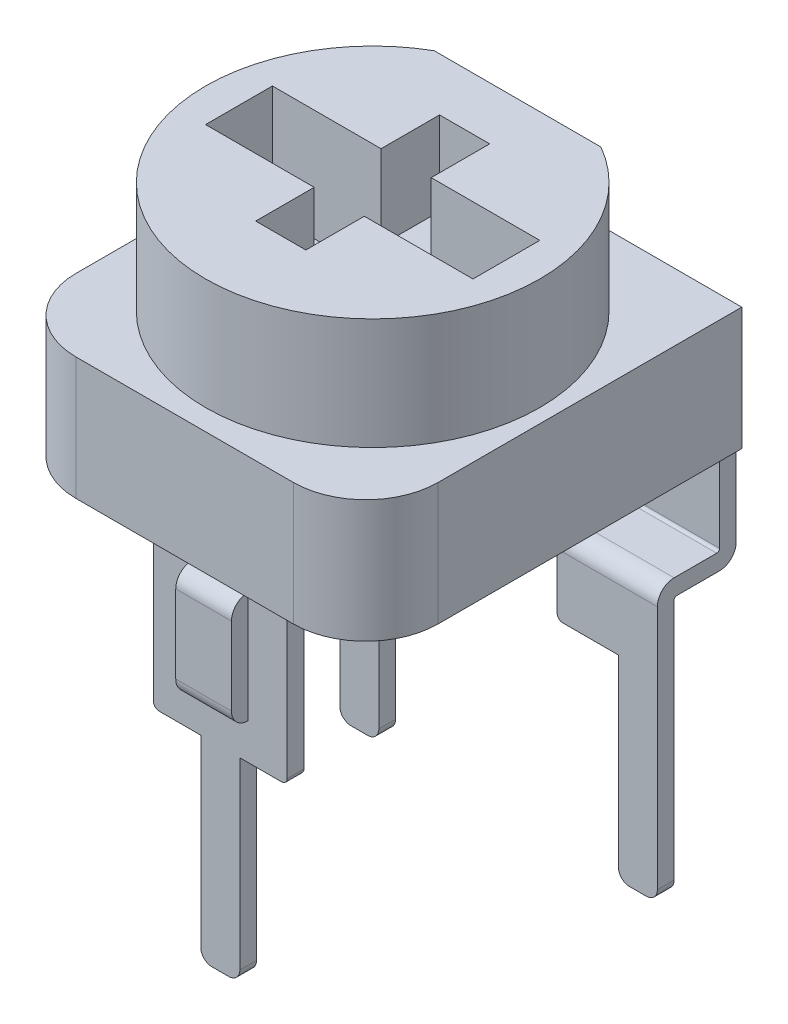
SolidWorks part; units mm, degrees
material "PVC Rigid"
ref_plane "Front Plane" through (0, 0, 0) normal (0, 0, 1) x (1, 0, 0)
ref_plane "Top Plane" through (0, 0, 0) normal (0, 1, 0) x (1, 0, 0)
ref_plane "Right Plane" through (0, 0, 0) normal (1, 0, 0) x (0, 0, -1)
sketch "Sketch1" plane through (0, 0, 0) normal (0, 1, 0) x (1, 0, 0)
  line L0 (-1.4967, 2.6) -> (1.4967, 2.6)
  arc A0 (-1.4967, 2.6) -> (1.4967, 2.6) centre (0, 0) ccw
  dimension "D1" = 6
  dimension "D2" = 2.6
extrude "Boss-Extrude1" add sketch "Sketch1" along normal blind 2
sketch "Sketch2" plane through (0, 2, 0) normal (0, 1, 0) x (1, 0, 0)
  line L1 (-2.4, -0.6) -> (2.4, -0.6)
  line L2 (-2.4, -0.6) -> (-2.4, 0.6)
  line L3 (-2.4, 0.6) -> (2.4, 0.6)
  line L4 (2.4, -0.6) -> (2.4, 0.6)
  line L5 (-2.4, -0.6) -> (2.4, 0.6) construction
  line L6 (-2.4, 0.6) -> (2.4, -0.6) construction
  point P0 (0, 0)
  point P6 (0, 0)
  dimension "D1" = 1.2
  dimension "D2" = 4.8
extrude "Cut-Extrude1" cut sketch "Sketch2" against normal through all
sketch "Sketch3" plane through (0, 2, 0) normal (0, 1, 0) x (1, 0, 0)
  line L1 (-0.45, -1.65) -> (0.45, -1.65)
  line L2 (-0.45, -1.65) -> (-0.45, 1.65)
  line L3 (-0.45, 1.65) -> (0.45, 1.65)
  line L4 (0.45, -1.65) -> (0.45, 1.65)
  line L5 (-0.45, -1.65) -> (0.45, 1.65) construction
  line L6 (-0.45, 1.65) -> (0.45, -1.65) construction
  point P0 (0, 0)
  dimension "D1" = 0.9
  dimension "D2" = 3.3
extrude "Cut-Extrude2" cut sketch "Sketch3" against normal blind 1.5
sketch "Sketch4" plane through (0, 0, 0) normal (0, -1, 0) x (1, 0, 0)
  line L1 (-3.25, -3.375) -> (3.25, -3.375)
  line L2 (-3.25, -3.375) -> (-3.25, 2.075)
  line L3 (-1.95, 3.375) -> (1.95, 3.375)
  line L4 (3.25, -3.375) -> (3.25, 2.075)
  line L5 (-3.25, -3.375) -> (2.8764, 2.987) construction
  line L6 (-2.8764, 2.987) -> (3.25, -3.375) construction
  arc A0 (-1.95, 3.375) -> (-3.25, 2.075) centre (-1.95, 2.075) ccw
  arc A1 (3.25, 2.075) -> (1.95, 3.375) centre (1.95, 2.075) ccw
  point P0 (0, 0)
  dimension "D3" = 1.95
  dimension "D4" = 6.5
  dimension "D1" = 2.6
  dimension "D2" = 2.075
  dimension "D5" = 3.375
extrude "Boss-Extrude2" add sketch "Sketch4" along normal blind 2.2 separate body
sketch "Sketch5" plane through (0, -2.2, 0) normal (0, -1, 0) x (1, 0, 0)
  line L1 (-1.2, 2.735) -> (1.2, 2.735)
  line L2 (-1.2, 2.735) -> (-1.2, 2.435)
  line L3 (-1.2, 2.435) -> (1.2, 2.435)
  line L4 (1.2, 2.735) -> (1.2, 2.435)
  line L5 (-1.2, 2.735) -> (1.2, 2.435) construction
  line L6 (-1.2, 2.435) -> (1.2, 2.735) construction
  point P0 (0, 2.585)
  dimension "D1" = 0.3
  dimension "D2" = 2.4
  dimension "D3" = 2.585
  dimension "D4" = 1.2
extrude "Boss-Extrude3" add sketch "Sketch5" along normal blind 3.2 separate body
sketch "Sketch6" plane through (0, -5.4, 0) normal (0, -1, 0) x (1, 0, 0)
  line L1 (-0.35, 2.435) -> (0.35, 2.435)
  line L2 (-0.35, 2.435) -> (-0.35, 2.735)
  line L3 (-0.35, 2.735) -> (0.35, 2.735)
  line L4 (0.35, 2.435) -> (0.35, 2.735)
  line L5 (-0.35, 2.435) -> (0.35, 2.735) construction
  line L6 (-0.35, 2.735) -> (0.35, 2.435) construction
  line L7 (1.2, 2.435) -> (1.2, 2.735) construction
  line L8 (1.2, 2.735) -> (-1.2, 2.735) construction
  point P0 (0, 2.585)
  dimension "D1" = 0.3
  dimension "D2" = 0.7
  dimension "D3" = 1.2
  dimension "D4" = 0.15
extrude "Boss-Extrude4" add sketch "Sketch6" along normal blind 3.5
fillet "Fillet1" radius 0.1 2 edges at (-1.2, -5.4, 2.585) (1.2, -5.4, 2.585)
fillet "Fillet2" radius 0.2 2 edges at (0.35, -8.9, 2.585) (-0.35, -8.9, 2.585)
sketch "Sketch8" plane through (0, 0, 2.735) normal (0, 0, 1) x (1, 0, 0)
  line L2 (-0.5, -2.75) -> (0.5, -2.75)
  line L3 (-0.5, -2.75) -> (-0.5, -4.75)
  line L4 (-0.5, -4.75) -> (0.5, -4.75)
  line L5 (0.5, -2.75) -> (0.5, -4.75)
  line L6 (-0.5, -2.75) -> (0.5, -4.75) construction
  line L8 (0, -2.2) -> (0, -8.9171) construction
  line L9 (-1.2, -3.75) -> (1.2, -3.75) construction
  line L10 (-1.2, -5.3) -> (-1.2, -2.2) construction
  line L11 (1.2, -5.3) -> (1.2, -2.2) construction
  line L12 (-0.5, -4.75) -> (0.5, -2.75) construction
  point P0 (0, -3.75)
  dimension "D1" = 1
  dimension "D2" = 2
extrude "Boss-Extrude5" add sketch "Sketch8" along normal blind 0.3
fillet "Fillet3" radius 0.3 2 edges at (0, -4.75, 3.035) (0, -2.75, 3.035)
sketch "Sketch16" plane through (0, 0, 2.435) normal (0, 0, -1) x (-1, 0, 0)
  line L0 (-0.4, -3.05) -> (0.4, -3.05)
  line L1 (-0.4, -3.05) -> (-0.4, -4.45)
  line L2 (-0.4, -4.45) -> (0.4, -4.45)
  line L3 (0.4, -3.05) -> (0.4, -4.45)
  line L4 (-0.4, -3.05) -> (0.4, -4.45) construction
  line L5 (0, -2.2) -> (0, -5.026) construction
  line L6 (1.2, -2.2) -> (-1.2, -2.2) construction
  line L7 (-0.4, -4.45) -> (0.4, -3.05) construction
  line L8 (-1.2, -3.75) -> (1.2, -3.75) construction
  line L9 (-1.2, -5.3) -> (-1.2, -2.2) construction
  line L10 (1.2, -5.3) -> (1.2, -2.2) construction
  point P0 (0, -3.75)
  dimension "D1" = 0.8
  dimension "D2" = 1.4
extrude "Cut-Extrude5" cut sketch "Sketch16" against normal blind 0.3
fillet "Fillet18" radius 0.3 2 edges at (0, -3.05, 2.735) (0, -4.45, 2.735)
sketch "Sketch9" plane through (0, 0, -3.375) normal (0, 0, -1) x (-1, 0, 0)
  line L1 (-2.85, -1) -> (-1.05, -1)
  line L2 (-2.85, -1) -> (-2.85, -4)
  line L3 (-2.85, -4) -> (-1.05, -4)
  line L4 (-1.05, -1) -> (-1.05, -4)
  line L5 (-2.85, -1) -> (-1.05, -4) construction
  line L6 (-2.85, -4) -> (-1.05, -1) construction
  line L9 (3.25, 0) -> (-3.25, 0) construction
  line L10 (0, 0) -> (0, -9.3004) construction
  line L11 (2.85, -1) -> (1.05, -4) construction
  line L12 (2.85, -4) -> (1.05, -1) construction
  line L13 (2.85, -4) -> (1.05, -4)
  line L14 (1.05, -1) -> (1.05, -4)
  line L15 (2.85, -1) -> (1.05, -1)
  line L16 (2.85, -1) -> (2.85, -4)
  point P0 (-1.95, -2.5)
  dimension "D1" = 1.8
  dimension "D2" = 3
  dimension "D3" = 1
  dimension "D4" = 2.1
extrude "Boss-Extrude6" add sketch "Sketch9" along normal blind 0.3 separate body
fillet "Fillet4" radius 0.3 1 edges at (1.95, -1, -3.675)
fillet "Fillet5" radius 0.3 1 edges at (-1.95, -1, -3.675)
sketch "Sketch10" plane through (0, -4, 0) normal (0, -1, 0) x (1, 0, 0)
  line L1 (-2.85, -3.675) -> (-1.05, -3.675)
  line L2 (-2.85, -3.675) -> (-2.85, -2.26)
  line L3 (-2.85, -2.26) -> (-1.05, -2.26)
  line L4 (-1.05, -3.675) -> (-1.05, -2.26)
  line L5 (1.05, -3.675) -> (2.85, -3.675)
  line L6 (1.05, -3.675) -> (1.05, -2.26)
  line L7 (1.05, -2.26) -> (2.85, -2.26)
  line L8 (2.85, -3.675) -> (2.85, -2.26)
  dimension "D1" = 1.415
  dimension "D2" = 1.8
  dimension "D3" = 1.415
  dimension "D4" = 1.8
extrude "Boss-Extrude7" add sketch "Sketch10" along normal blind 0.3
fillet "Fillet6" radius 0.3 1 edges at (-1.95, -4.3, -3.675)
fillet "Fillet7" radius 0.3 1 edges at (1.95, -4.3, -3.675)
fillet "Fillet8" radius 0.05 1 edges
fillet "Fillet9" radius 0.05 1 edges
sketch "Sketch11" plane through (0, -4.3, 0) normal (0, -1, 0) x (1, 0, 0)
  line L0 (-1.05, -3.375) -> (-1.05, -2.26) construction
  line L1 (-2.85, -2.26) -> (-1.05, -2.26)
  line L2 (-2.85, -2.26) -> (-2.85, -2.56)
  line L3 (-2.85, -2.56) -> (-1.05, -2.56)
  line L4 (-1.05, -2.26) -> (-1.05, -2.56)
  line L5 (0, -1.9185) -> (0, -4.5857) construction
  line L6 (1.05, -2.26) -> (1.05, -2.56)
  line L7 (2.85, -2.56) -> (1.05, -2.56)
  line L8 (2.85, -2.26) -> (2.85, -2.56)
  line L9 (2.85, -2.26) -> (1.05, -2.26)
  dimension "D1" = 0.3
extrude "Boss-Extrude8" add sketch "Sketch11" along normal blind 1.1
fillet "Fillet10" radius 0.3 1 edges at (-1.95, -4, -2.26)
fillet "Fillet11" radius 0.3 1 edges at (1.95, -4, -2.26)
fillet "Fillet12" radius 0.05 1 edges at (1.95, -4.3, -2.56)
fillet "Fillet13" radius 0.05 1 edges at (-1.95, -4.3, -2.56)
sketch "Sketch13" plane through (2.1208, -5.4, -5.8465) normal (0, -1, 0) x (1, 0, 0)
  line L0 (0.7292, 3.2865) -> (0.7292, 3.5865) construction
  line L1 (0.0292, 3.2865) -> (0.7292, 3.2865)
  line L2 (0.0292, 3.2865) -> (0.0292, 3.5865)
  line L3 (0.0292, 3.5865) -> (0.7292, 3.5865)
  line L4 (0.7292, 3.2865) -> (0.7292, 3.5865)
  line L5 (0.0292, 3.2865) -> (0.7292, 3.5865) construction
  line L6 (0.0292, 3.5865) -> (0.7292, 3.2865) construction
  line L7 (0.7292, 3.5865) -> (-1.0708, 3.5865) construction
  point P0 (0.3792, 3.4365)
  dimension "D1" = 0.3
  dimension "D2" = 0.7
  dimension "D3" = 0.35
  dimension "D4" = 0.15
extrude "Boss-Extrude9" add sketch "Sketch13" along normal blind 3.5
fillet "Fillet14" radius 0.2 2 edges at (2.85, -8.9, -2.41) (2.15, -8.9, -2.41)
sketch "Sketch15" plane through (-2.2614, -5.4, -5.8201) normal (0, -1, 0) x (1, 0, 0)
  line L0 (1.2114, 3.5601) -> (-0.5886, 3.5601) construction
  line L1 (-0.5886, 3.2601) -> (0.1114, 3.2601)
  line L2 (-0.5886, 3.2601) -> (-0.5886, 3.5601)
  line L3 (-0.5886, 3.5601) -> (0.1114, 3.5601)
  line L4 (0.1114, 3.2601) -> (0.1114, 3.5601)
  line L5 (-0.5886, 3.2601) -> (0.1114, 3.5601) construction
  line L6 (-0.5886, 3.5601) -> (0.1114, 3.2601) construction
  line L7 (-0.5886, 3.5601) -> (-0.5886, 3.2601) construction
  point P0 (-0.2386, 3.4101)
  dimension "D1" = 0.3
  dimension "D2" = 0.7
  dimension "D3" = 0.15
  dimension "D4" = 0.35
extrude "Boss-Extrude10" add sketch "Sketch15" along normal blind 3.5
fillet "Fillet15" radius 0.2 2 edges at (-2.15, -8.9, -2.41) (-2.85, -8.9, -2.41)
fillet "Fillet16" radius 0.1 1 edges at (1.05, -5.4, -2.41)
fillet "Fillet17" radius 0.1 1 edges at (-1.05, -5.4, -2.41)
